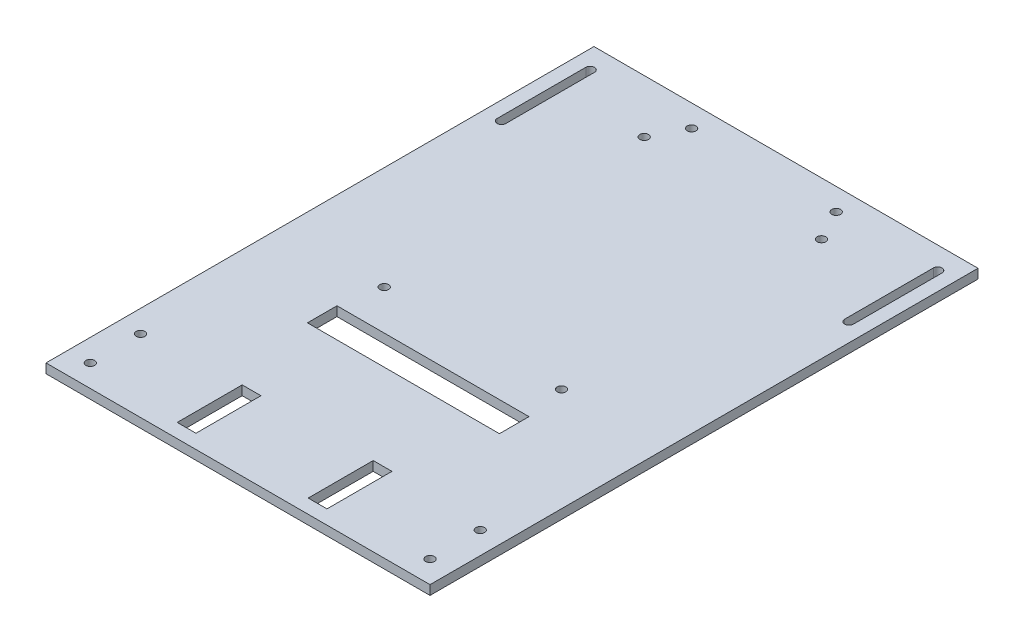
SolidWorks part; units mm, degrees
ref_plane "Front Plane" through (0, 0, 0) normal (0, 0, 1) x (1, 0, 0)
ref_plane "Top Plane" through (0, 0, 0) normal (0, 1, 0) x (1, 0, 0)
ref_plane "Right Plane" through (0, 0, 0) normal (1, 0, 0) x (0, 0, -1)
sketch "Sketch1" plane through (0, 0, 0) normal (0, 1, 0) x (1, 0, 0)
  line L1 (-65, -92.25) -> (65, -92.25)
  line L2 (-65, -92.25) -> (-65, 92.25)
  line L3 (-65, 92.25) -> (65, 92.25)
  line L4 (65, -92.25) -> (65, 92.25)
  line L5 (-65, -92.25) -> (65, 92.25) construction
  line L6 (-65, 92.25) -> (65, -92.25) construction
  point P0 (0, 0)
  dimension "D1" = 130
  dimension "D2" = 184.5
extrude "Boss-Extrude1" add sketch "Sketch1" along normal blind 3.175
sketch "Sketch4" plane through (0, 0, 0) normal (0, -1, 0) x (-1, 0, 0)
  line L6 (-58.825, 85.775) -> (-58.825, 55.775) construction
  line L7 (-57.35, 85.775) -> (-57.35, 55.775)
  line L8 (-60.3, 85.775) -> (-60.3, 55.775)
  line L36 (-65, -92.25) -> (-65, 92.25) construction
  line L46 (-65, 92.25) -> (65, 92.25) construction
  line L48 (58.825, 85.775) -> (58.825, 55.775) construction
  line L49 (60.3, 85.775) -> (60.3, 55.775)
  line L50 (57.35, 85.775) -> (57.35, 55.775)
  line L54 (65, 92.25) -> (65, -92.25) construction
  line L55 (65, -92.25) -> (-65, -92.25) construction
  arc A14 (-57.35, 85.775) -> (-60.3, 85.775) centre (-58.825, 85.775) ccw
  arc A15 (-60.3, 55.775) -> (-57.35, 55.775) centre (-58.825, 55.775) ccw
  circle A18 centre (-57.5, -84.75) radius 1.475
  circle A19 centre (-57.5, -67.75) radius 1.475
  arc A51 (60.3, 85.775) -> (57.35, 85.775) centre (58.825, 85.775) ccw
  arc A52 (57.35, 55.775) -> (60.3, 55.775) centre (58.825, 55.775) ccw
  circle A55 centre (57.5, -84.75) radius 1.475
  circle A56 centre (57.5, -67.75) radius 1.475
  point P2 (-58.825, 70.775)
  point P82 (58.825, 70.775)
  point P96 (-58.825, 87.25)
  point P100 (58.825, 87.25)
  dimension "D1" = 4.7
  dimension "D21" = 2.95
  dimension "D22" = 2.95
  dimension "D23" = 2.95
  dimension "D24" = 2.95
  dimension "D25" = 1.475
  dimension "D47" = 1.475
  dimension "D50" = 5
  dimension "D51" = 7.5
  dimension "D52" = 7.5
  dimension "D53" = 7.5
  dimension "D56" = 7.5
  dimension "D57" = 7.5
  dimension "D58" = 7.5
  dimension "D20" = 30
  dimension "D34" = 30
  dimension "D45" = 5
  dimension "D49" = 4.7
  dimension "D54" = 17
  dimension "D55" = 17
extrude "Cut-Extrude3" cut sketch "Sketch4" against normal through all
sketch "Sketch5" plane through (0, 0, 0) normal (0, -1, 0) x (1, 0, 0)
  line L0 (-23, -81.6775) -> (-23, -89.8725)
  line L1 (23, -91.5608) -> (23, -79.9892)
  line L3 (-28.3353, -87.25) -> (-20.6147, -87.25)
  line L4 (65, -92.25) -> (-65, -92.25) construction
  line L5 (65, -92.25) -> (-65, -92.25) construction
  circle A0 centre (-24.475, -85.775) radius 1.475
  circle A1 centre (24.475, -85.775) radius 1.475
  point P7 (-23.1414, -85.1449)
  point P10 (23, -85.775)
  point P16 (-24.475, -87.25)
  point P19 (-23, -85.775)
  point P21 (0, -92.25)
  dimension "D2" = 2.95
  dimension "D3" = 2.95
  dimension "D6" = 6.475
  dimension "D1" = 46
  dimension "D4" = 23
  dimension "D5" = 5
extrude "Cut-Extrude4" cut sketch "Sketch5" against normal blind 10 contours A0 | A1 region at (-24.475, 0, -85.775) region at (24.475, 0, -85.775)
sketch "Sketch6" plane through (0, 0, -92.25) normal (0, 0, -1) x (-1, 0, 0)
  line L1 (-65, 0) -> (65, 0)
  line L2 (-65, 0) -> (-65, 3.175)
  line L3 (-65, 3.175) -> (65, 3.175)
  line L4 (65, 0) -> (65, 3.175)
extrude "Boss-Extrude2" add sketch "Sketch6" along normal blind 1
sketch "Sketch7" plane through (0, 3.175, 0) normal (0, 1, 0) x (1, 0, 0)
  line L0 (-65, 93.25) -> (-65, -92.25) construction
  line L6 (-65, -92.25) -> (65, -92.25) construction
  line L7 (-25.35, -87.4884) -> (-19, -87.4884)
  line L8 (-25.35, -87.4884) -> (-25.35, -65.4884)
  line L9 (-25.35, -65.4884) -> (-19, -65.4884)
  line L10 (-19, -87.4884) -> (-19, -65.4884)
  line L11 (65, -92.25) -> (65, 93.25) construction
  line L12 (19, -87.4884) -> (25.35, -87.4884)
  line L13 (19, -87.4884) -> (19, -65.4884)
  line L14 (19, -65.4884) -> (25.35, -65.4884)
  line L15 (25.35, -87.4884) -> (25.35, -65.4884)
  dimension "D1" = 22
  dimension "D2" = 6.35
  dimension "D3" = 4.7616
  dimension "D4" = 39.65
  dimension "D5" = 6.35
  dimension "D6" = 22
  dimension "D7" = 4.7616
  dimension "D8" = 39.65
extrude "Cut-Extrude5" cut sketch "Sketch7" against normal through all both and the other way through all
sketch "Sketch8" plane through (0, 0, 0) normal (0, -1, 0) x (1, 0, 0)
  line L0 (-32.5, 92.25) -> (-32.5, 36.25)
  line L1 (-65, 92.25) -> (65, 92.25) construction
  line L3 (-32.5, 36.25) -> (32.5, 36.25)
  line L4 (-32.5, 36.25) -> (-32.5, 26.25)
  line L5 (-32.5, 26.25) -> (32.5, 26.25)
  line L6 (32.5, 36.25) -> (32.5, 26.25)
  line L7 (65, 92.25) -> (65, -93.25) construction
  dimension "D1" = 56
  dimension "D2" = 10
  dimension "D3" = 65
  dimension "D4" = 32.5
extrude "Cut-Extrude6" cut sketch "Sketch8" against normal blind 10 contours L6 L3 L4 L5 region at (0, 0, 31.25)
sketch "Sketch9" plane through (0, 0, 0) normal (0, -1, 0) x (-1, 0, 0)
  line L0 (-65, -92.25) -> (-65, 93.25) construction
  line L1 (30, 75.25) -> (-30, 75.25)
  line L2 (30, 75.25) -> (30, -12.75)
  line L3 (30, -12.75) -> (-30, -12.75)
  line L4 (-30, 75.25) -> (-30, -12.75)
  line L5 (30, 75.25) -> (-30, -12.75) construction
  line L6 (30, -12.75) -> (-30, 75.25) construction
  line L7 (-65, 93.25) -> (65, 93.25) construction
  circle A0 centre (30, -12.75) radius 1.475
  circle A1 centre (-30, -12.75) radius 1.475
  circle A2 centre (-30, 75.25) radius 1.475
  circle A3 centre (30, 75.25) radius 1.475
  point P0 (0, 31.25)
  dimension "D4" = 2.95
  dimension "D5" = 2.95
  dimension "D6" = 2.95
  dimension "D7" = 2.95
  dimension "D1" = 60
  dimension "D2" = 88
  dimension "D3" = 18
  dimension "D8" = 65
  dimension "D9" = 88
  dimension "D10" = 60
extrude "Cut-Extrude7" cut sketch "Sketch9" against normal blind 75 contours L4 A1 L3 | L1 A2 L4 | L4 A2 L1 | A0 | A2 | A1 | A3 region at (29.374, 0, -74.624) region at (30.2087, 0, -75.4587) region at (30.2087, 0, 12.9587)
